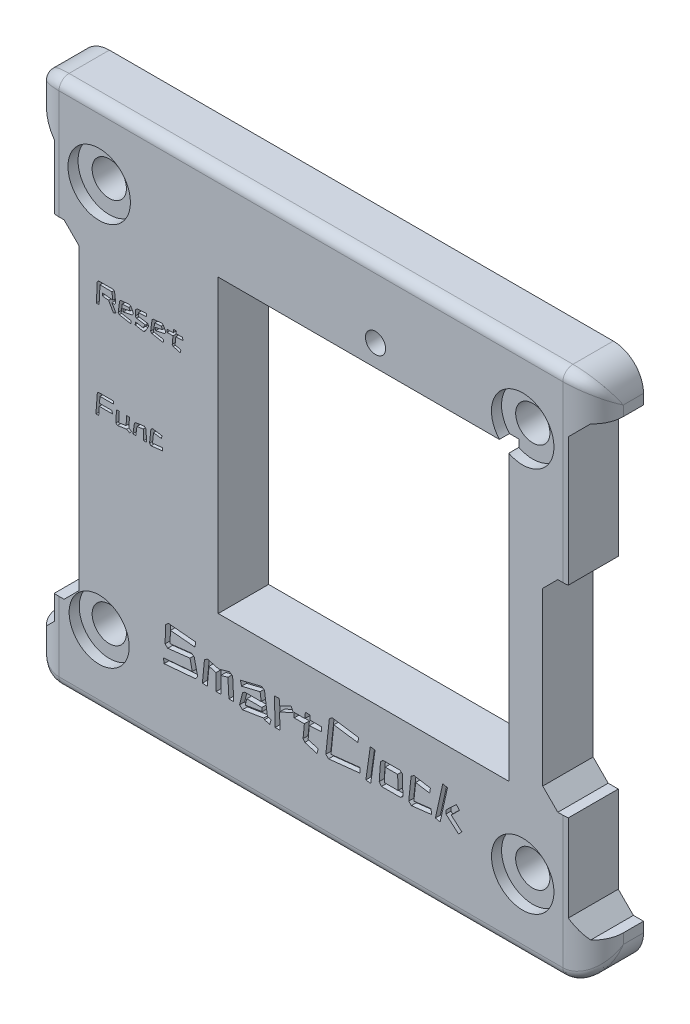
SolidWorks part; units mm, degrees
ref_plane "前视基准面" through (0, 0, 0) normal (0, 0, 1) x (1, 0, 0)
ref_plane "上视基准面" through (0, 0, 0) normal (0, 1, 0) x (1, 0, 0)
ref_plane "右视基准面" through (0, 0, 0) normal (1, 0, 0) x (0, 0, -1)
other "Configuration Table"
sketch "草图2" plane through (0, 0, 0) normal (0, 0, 1) x (1, 0, 0)
  line L1 (163.5891, -115.0663) -> (205.6006, -115.0663) construction
  line L2 (161.5891, -117.0663) -> (161.5891, -155.4356) construction
  line L3 (163.5891, -157.4356) -> (205.6006, -157.4356) construction
  line L4 (207.6006, -117.0663) -> (207.6006, -155.4356) construction
  line L9 (156.5891, -110.0663) -> (212.6006, -110.0663)
  line L10 (156.5891, -110.0663) -> (156.5891, -162.4356)
  line L11 (156.5891, -162.4356) -> (212.6006, -162.4356)
  line L12 (212.6006, -110.0663) -> (212.6006, -162.4356)
  arc A0 (161.5891, -155.4356) -> (163.5891, -157.4356) centre (163.5891, -155.4356) ccw construction
  arc A1 (205.6006, -157.4356) -> (207.6006, -155.4356) centre (205.6006, -155.4356) ccw construction
  arc A2 (205.6006, -115.0663) -> (207.6006, -117.0663) centre (205.6006, -117.0663) cw construction
  arc A3 (163.5891, -115.0663) -> (161.5891, -117.0663) centre (163.5891, -117.0663) ccw construction
  dimension "D5" = 2
  dimension "D6" = 5
  dimension "D7" = 5
  dimension "D8" = 5
  dimension "D9" = 5
extrude "凸台-拉伸3" add sketch "草图2" along normal blind 5
sketch "草图3" plane through (0, 0, 5) normal (0, 0, 1) x (1, 0, 0)
  line L0 (156.5891, -110.0663) -> (212.6006, -162.4356) construction
  line L1 (212.6006, -110.0663) -> (156.5891, -162.4356) construction
  line L3 (163.5764, -155.385) -> (205.6134, -155.385) construction
  line L4 (163.5764, -155.385) -> (163.5764, -117.117) construction
  line L5 (163.5764, -117.117) -> (205.6134, -117.117) construction
  line L6 (205.6134, -155.385) -> (205.6134, -117.117) construction
  line L7 (184.5949, -117.117) -> (184.5949, -155.385) construction
  line L8 (163.5764, -136.251) -> (205.6134, -136.251) construction
  circle A0 centre (163.5764, -117.117) radius 1.7
  circle A1 centre (205.6134, -117.117) radius 1.7
  circle A2 centre (163.5764, -155.385) radius 1.7
  circle A3 centre (205.6134, -155.385) radius 1.7
  point P8 (184.5949, -136.251)
  dimension "D3" = 3.4
  dimension "D4" = 3.4
  dimension "D5" = 3.4
  dimension "D6" = 3.4
  dimension "D1" = 42.037
  dimension "D2" = 38.268
extrude "切除-拉伸1" cut sketch "草图3" against normal through all
sketch "草图4" plane through (0, 0, 5) normal (0, 0, 1) x (1, 0, 0)
  line L1 (175.394, -119.176) -> (204.2319, -119.176)
  line L2 (175.394, -119.176) -> (175.394, -148.0925)
  line L3 (175.394, -148.0925) -> (204.2319, -148.0925)
  line L4 (204.2319, -119.176) -> (204.2319, -148.0925)
extrude "切除-拉伸2" cut sketch "草图4" against normal through all
sketch "草图5" plane through (156.5891, 0, 0) normal (-1, 0, 0) x (0, 0, 1)
  line L0 (-10.6001, -154.5215) -> (-0.6001, -154.5215) construction
  line L1 (-9.1001, -141.0215) -> (-3.1001, -141.0215)
  line L2 (-9.1001, -141.0215) -> (-9.1001, -154.5215)
  line L3 (-9.1001, -154.5215) -> (5.7253, -154.5215)
  line L5 (5.7253, -121.904) -> (5.7253, -154.5215)
  line L6 (-3.1001, -121.904) -> (5.7253, -121.904)
  line L7 (-3.1001, -121.904) -> (-3.1001, -141.0215)
  line L11 (-0.6001, -121.904) -> (-4.6001, -121.904) construction
  dimension "D2" = 0
  dimension "D3" = 0
extrude "切除-拉伸3" cut sketch "草图5" against normal blind 5
sketch "草图6" plane through (0, 0, 0) normal (0, 0, -1) x (-1, 0, 0)
  line L0 (-161.5891, -121.904) -> (-161.5891, -154.5215) construction
  line L1 (-161.5891, -123.8211) -> (-167.7327, -123.8211)
  line L2 (-161.5891, -123.8211) -> (-161.5891, -129.3459)
  line L3 (-161.5891, -129.3459) -> (-167.7327, -129.3459)
  line L4 (-167.7327, -123.8211) -> (-167.7327, -129.3459)
  line L6 (-161.5891, -133.3707) -> (-167.7327, -133.3707)
  line L7 (-161.5891, -133.3707) -> (-161.5891, -138.9567)
  line L8 (-161.5891, -138.9567) -> (-167.7327, -138.9567)
  line L9 (-167.7327, -133.3707) -> (-167.7327, -138.9567)
extrude "切除-拉伸4" cut sketch "草图6" against normal blind 2.5
sketch "草图7" plane through (156.5891, 0, 0) normal (-1, 0, 0) x (0, 0, 1)
  line L1 (5.7316, -114.0663) -> (-0.6338, -114.0663)
  line L2 (5.7316, -114.0663) -> (5.7316, -158.4356)
  line L3 (5.7316, -158.4356) -> (-0.6338, -158.4356)
  line L4 (-0.6338, -114.0663) -> (-0.6338, -158.4356)
  line L5 (5, -162.4356) -> (0, -162.4356) construction
  line L6 (5, -110.0663) -> (0, -110.0663) construction
  dimension "D1" = 4
  dimension "D2" = 4
extrude "切除-拉伸5" cut sketch "草图7" against normal blind 2.5
sketch "草图8" plane through (212.6006, 0, 0) normal (1, 0, 0) x (0, 0, -1)
  line L0 (-5, -110.0663) -> (0, -110.0663) construction
  line L1 (-8.7986, -114.0663) -> (3.2654, -114.0663)
  line L2 (-8.7986, -114.0663) -> (-8.7986, -158.4356)
  line L3 (-8.7986, -158.4356) -> (3.2654, -158.4356)
  line L4 (3.2654, -114.0663) -> (3.2654, -158.4356)
  line L5 (-5, -162.4356) -> (0, -162.4356) construction
  dimension "D1" = 4
  dimension "D2" = 4
extrude "切除-拉伸6" cut sketch "草图8" against normal blind 2.5
sketch "草图9" plane through (212.6006, 0, 0) normal (1, 0, 0) x (0, 0, -1)
  line L0 (9.6001, -148.3238) -> (-8.0457, -148.3238)
  line L1 (9.6001, -128.3238) -> (-8.0457, -128.3238)
  line L2 (9.6001, -128.3238) -> (9.6001, -148.3238)
  line L4 (-8.0457, -128.3238) -> (-8.0457, -148.3238)
extrude "切除-拉伸7" cut sketch "草图9" against normal blind 5
chamfer "倒角1" distance 1.5 angle 45 8 edges at (210.1006, -158.4356, 2.5) (207.6006, -148.3238, 2.5) (207.6006, -128.3238, 2.5) (210.1006, -114.0663, 2.5) (159.0891, -114.0663, 2.5) (159.0891, -158.4356, 2.5) (161.5891, -154.5215, 2.5) (161.5891, -121.904, 2.5)
fillet "圆角1" radius 3 8 edges at (156.5891, -112.0663, 5) (156.5891, -110.0663, 2.5) (212.6006, -110.0663, 2.5) (212.6006, -112.0663, 5) (212.6006, -160.4356, 5) (212.6006, -162.4356, 2.5) (156.5891, -162.4356, 2.5) (156.5891, -160.4356, 5)
sketch "草图10" plane through (0, 0, 5) normal (0, 0, 1) x (1, 0, 0)
  circle A0 centre (163.5764, -155.385) radius 2.9808
  circle A1 centre (205.6132, -155.3848) radius 3.1
  circle A2 centre (399.9851, -296.3455) radius 3.1
  circle A3 centre (594.146, -437.3272) radius 3.1
  circle A4 centre (163.5764, -117.117) radius 3.1
  circle A5 centre (205.6134, -117.117) radius 3.1
  dimension "D1" = 5.9617
extrude "切除-拉伸8" cut sketch "草图10" against normal blind 1
sketch "草图11" plane through (0, 0, 5) normal (0, 0, 1) x (1, 0, 0)
  text T0 "SmartClock" font "ZCOOL KuaiLe" height 3.5
  text T1 "Func" font "ZCOOL KuaiLe" height 2
  text T2 "Reset" font "ZCOOL KuaiLe" height 2
extrude "切除-拉伸9" cut sketch "草图11" against normal blind 0.5
sketch "草图12" plane through (0, 0, 0) normal (0, 0, -1) x (-1, 0, 0)
  line L1 (-201.3036, -115.1297) -> (-184.4877, -115.1297)
  line L2 (-201.3036, -115.1297) -> (-201.3036, -119.3071)
  line L3 (-201.3036, -119.3071) -> (-184.4877, -119.3071)
  line L4 (-184.4877, -115.1297) -> (-184.4877, -119.3071)
  line L5 (-163.5764, -115.1296) -> (-205.6133, -115.1297) construction
extrude "切除-拉伸10" cut sketch "草图12" against normal blind 1.5
sketch "草图13" plane through (0, 0, 1.5) normal (0, 0, -1) x (-1, 0, 0)
  circle A0 centre (-191.0083, -117.0307) radius 1
extrude "切除-拉伸11" cut sketch "草图13" against normal through all
fillet "圆角2" radius 1 6 edges at (157.4678, -110.945, 4.1213) (184.5949, -110.0663, 5) (211.7219, -110.945, 4.1213) (211.7219, -161.5569, 4.1213) (157.4678, -161.5569, 4.1213) (184.5949, -162.4356, 5)
